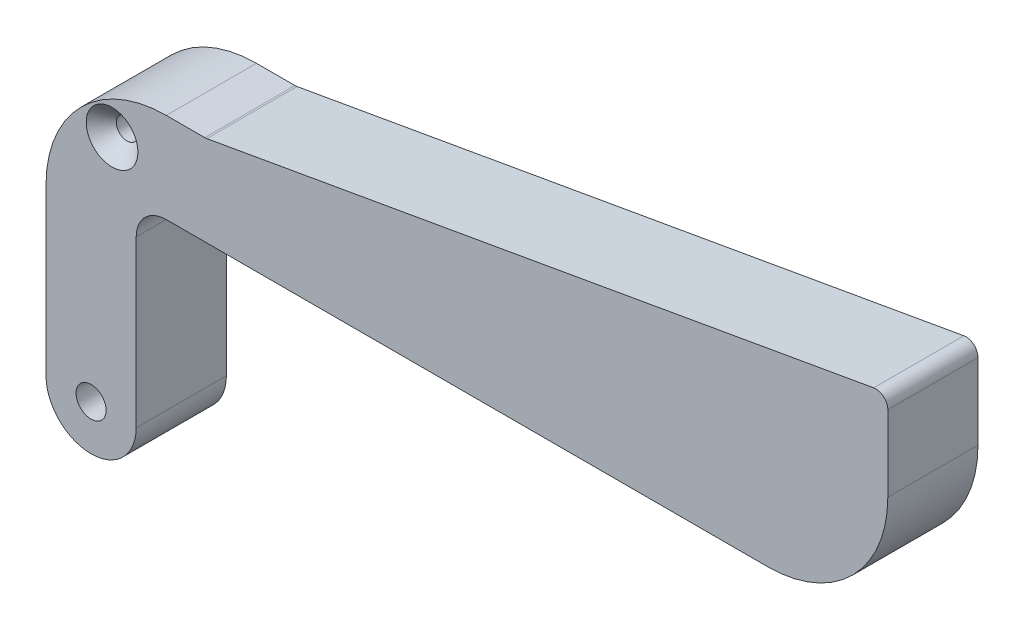
SolidWorks part; units mm, degrees
ref_plane "Front Plane" through (0, 0, 0) normal (0, 0, 1) x (1, 0, 0)
ref_plane "Top Plane" through (0, 0, 0) normal (0, 1, 0) x (1, 0, 0)
ref_plane "Right Plane" through (0, 0, 0) normal (1, 0, 0) x (0, 0, -1)
sketch "Sketch1" plane through (0, 0, 0) normal (0, 0, 1) x (1, 0, 0)
  line L1 (0, 0) -> (177.8, 0)
  line L2 (0, 0) -> (0, 19.05)
  line L4 (177.8, 0) -> (177.8, 44.45)
  line L5 (33.7494, 19.05) -> (0, 19.05)
  line L6 (177.8, 44.45) -> (33.7494, 19.05)
  dimension "D1" = 19.05
  dimension "D2" = 25.4
  dimension "D3" = 10
  dimension "D4" = 177.8
extrude "Boss-Extrude1" add sketch "Sketch1" along normal blind 19.05
sketch "Sketch4" plane through (0, 0, 19.05) normal (0, 0, 1) x (1, 0, 0)
  line L0 (0, 19.05) -> (0, 0) construction
  line L1 (0, 0) -> (19.05, 0)
  line L2 (0, 0) -> (0, -50.8)
  line L3 (0, -50.8) -> (19.05, -50.8)
  line L4 (19.05, 0) -> (19.05, -50.8)
  dimension "D1" = 50.8
extrude "Boss-Extrude2" add sketch "Sketch4" against normal up to surface (19.05 mm away) contours L2 L3 L4 L1 up to face at (77.8699, 16.51, 0)
fillet "Fillet1" radius 2.54 2 edges at (33.7494, 19.05, 9.525) (177.8, 44.45, 9.525)
sketch "Sketch2" plane through (0, 0, 19.05) normal (0, 0, 1) x (1, 0, 0)
  line L0 (0, -41.275) -> (9.525, -41.275) construction
  line L2 (9.525, -41.275) -> (19.05, -41.275) construction
  line L3 (19.05, 0) -> (19.05, -50.8) construction
  line L4 (9.525, -41.275) -> (9.525, -50.8) construction
  line L5 (0, -50.8) -> (19.05, -50.8) construction
  circle A0 centre (9.525, -41.275) radius 3.175
  point P2 (0, 0)
extrude "Cut-Extrude1" cut sketch "Sketch2" against normal through all
fillet "Fillet2" radius 25.4 1 edges at (177.8, 0, 9.525)
fillet "Fillet3" radius 25.4 1 edges at (0, 19.05, 9.525)
fillet "Fillet4" radius 6.35 1 edges at (19.05, 0, 9.525)
fillet "Fillet5" radius 9.525 2 edges at (19.05, -50.8, 9.525) (0, -50.8, 9.525)
sketch "Sketch6" plane through (0, 0, 19.05) normal (0, 0, 1) x (1, 0, 0)
  line L0 (9.525, -41.275) -> (13.9525, 9.3317) construction
  line L1 (19.05, -6.35) -> (19.05, -41.275) construction
  circle A0 centre (13.9525, 9.3317) radius 2.286
  dimension "D3" = 4.572
  dimension "D1" = 5
  dimension "D2" = 50.8
extrude "Cut-Extrude3" cut sketch "Sketch6" against normal through all
chamfer "Chamfer1" distance 3.175 angle 45 1 edges at (16.2385, 9.3317, 19.05)
